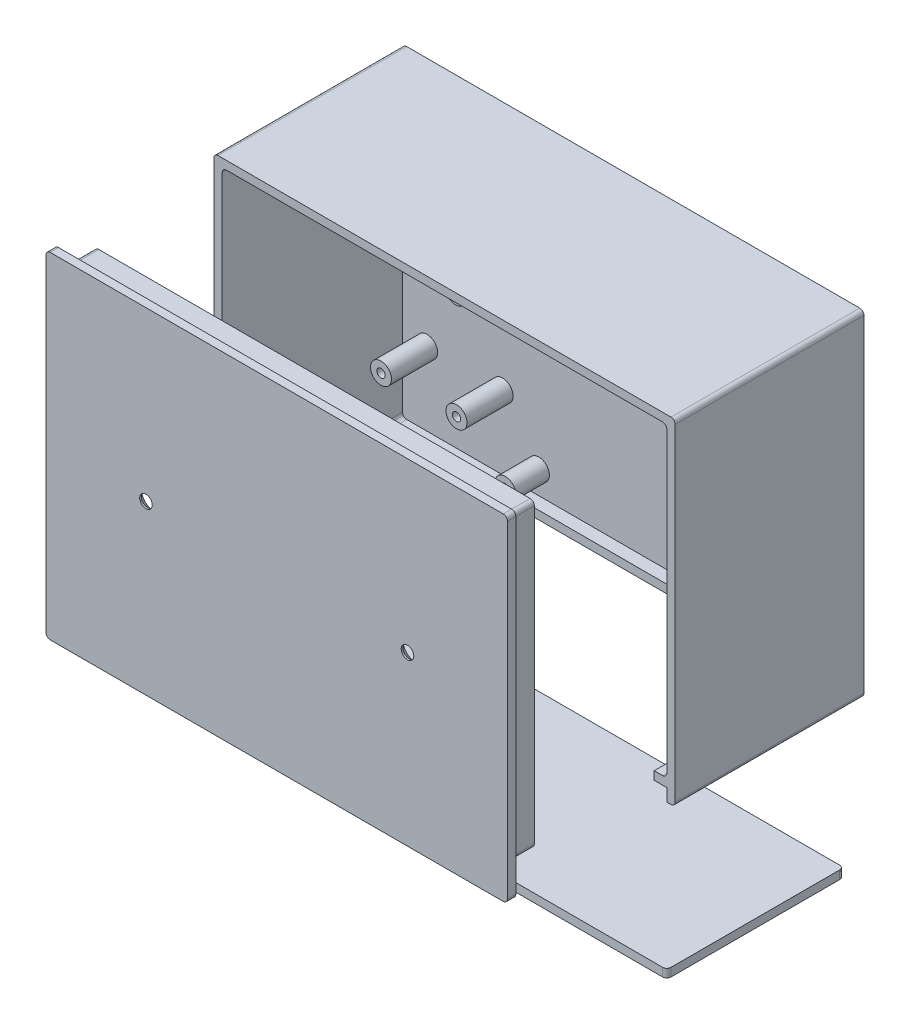
SolidWorks part; units mm, degrees
ref_plane "Спереди" through (0, 0, 0) normal (0, 0, 1) x (1, 0, 0)
ref_plane "Сверху" through (0, 0, 0) normal (0, 1, 0) x (1, 0, 0)
ref_plane "Справа" through (0, 0, 0) normal (1, 0, 0) x (0, 0, -1)
sketch "Эскиз1" plane through (0, 0, 0) normal (0, 0, 1) x (1, 0, 0)
  line L0 (-55, -41.511) -> (-53, -41.511)
  line L2 (-55, 38.489) -> (-55, -41.511)
  line L5 (-55, 38.489) -> (55, 38.489)
  line L6 (53, -36.511) -> (53, 36.489)
  line L7 (-53, -41.511) -> (-53, -38.511)
  line L8 (-53, -38.511) -> (-50, -38.511)
  line L9 (-50, -38.511) -> (-50, -36.511)
  line L10 (-50, -36.511) -> (-53, -36.511)
  line L11 (-53, -36.511) -> (-53, 36.489)
  line L12 (-53, 36.489) -> (53, 36.489)
  line L13 (0, 55.7111) -> (0, -96.3987) construction
  line L14 (50, -36.511) -> (53, -36.511)
  line L15 (50, -38.511) -> (50, -36.511)
  line L16 (53, -38.511) -> (50, -38.511)
  line L17 (53, -41.511) -> (53, -38.511)
  line L18 (55, 38.489) -> (55, -41.511)
  line L19 (55, -41.511) -> (53, -41.511)
  point P0 (0, 0)
  point P15 (0, 36.489)
  point P21 (0, 38.489)
  dimension "D1" = 2
  dimension "D2" = 2
  dimension "D3" = 2
  dimension "D4" = 55
  dimension "D5" = 80
  dimension "D6" = 2
  dimension "D7" = 3
  dimension "D8" = 3
extrude "Бобышка-Вытянуть3" add sketch "Эскиз1" along normal blind 43
sketch "Эскиз2" plane through (0, 0, 0) normal (0, 0, -1) x (-1, 0, 0)
  line L36 (55, 38.489) -> (55, -41.511) construction
  line L37 (-55, 38.489) -> (55, 38.489) construction
  line L38 (-55, -41.511) -> (-55, 38.489) construction
  line L39 (55, 38.489) -> (55, -41.511)
  line L40 (-55, 38.489) -> (55, 38.489)
  line L41 (-55, -41.511) -> (-55, 38.489)
  line L42 (-55, -41.511) -> (55, -41.511)
extrude "Бобышка-Вытянуть4" add sketch "Эскиз2" along normal blind 2
ref_plane "Плоскость1" through (0, 0, 8) normal (0, 0, 1) x (1, 0, 0)
sketch "Эскиз3" plane through (0, 0, 8) normal (0, 0, 1) x (1, 0, 0)
  line L0 (-53, -38.511) -> (-50, -38.511) construction
  line L1 (48, -32.511) -> (-23, -32.511) construction
  line L2 (48, -32.511) -> (48, 17.489) construction
  line L3 (48, 17.489) -> (-23, 17.489) construction
  line L4 (-23, -32.511) -> (-23, 17.489) construction
  line L5 (-33.1063, -7.511) -> (53.7568, -7.511) construction
  line L6 (12.5, 27.0434) -> (12.5, -35.2357) construction
  line L8 (50, -38.511) -> (53, -38.511) construction
  line L9 (53, 36.489) -> (53, -36.511) construction
  line L10 (-38.1409, 10.489) -> (-38.1409, -27.511) construction
  line L11 (-49.1409, 10.489) -> (-27.1409, 10.489) construction
  line L12 (-49.1409, 10.489) -> (-49.1409, -27.511) construction
  line L13 (-49.1409, -27.511) -> (-27.1409, -27.511) construction
  line L14 (-27.1409, 10.489) -> (-27.1409, -27.511) construction
  circle A0 centre (-20.5, 15.989) radius 1
  circle A1 centre (-20.5, 15.989) radius 2.5
  circle A2 centre (45.5, 15.989) radius 2.5
  circle A3 centre (45.5, 15.989) radius 1
  circle A4 centre (-20.5, 15.989) radius 1
  circle A5 centre (-20.5, 15.989) radius 2.5
  circle A6 centre (45.5, 15.989) radius 2.5
  circle A7 centre (45.5, 15.989) radius 1
  circle A8 centre (45.5, -31.011) radius 1
  circle A9 centre (45.5, -31.011) radius 2.5
  circle A10 centre (-20.5, -31.011) radius 2.5
  circle A11 centre (-20.5, -31.011) radius 1
  circle A12 centre (45.5, -31.011) radius 1
  circle A13 centre (45.5, -31.011) radius 2.5
  circle A14 centre (-20.5, -31.011) radius 2.5
  circle A15 centre (-20.5, -31.011) radius 1
  circle A16 centre (-47.1409, -19.011) radius 1
  circle A17 centre (-47.1409, -19.011) radius 2.5
  circle A18 centre (-29.1409, -19.011) radius 2.5
  circle A19 centre (-29.1409, -19.011) radius 1
  circle A20 centre (-29.3409, 6.489) radius 2.5
  circle A21 centre (-29.3409, 6.489) radius 1
  point P0 (12.5, -7.511)
  point P35 (12.5, 17.489)
  point P36 (-23, -7.511)
  point P40 (-38.1409, -8.8408)
  dimension "D5" = 2
  dimension "D6" = 5
  dimension "D11" = 2
  dimension "D12" = 5
  dimension "D1" = 50
  dimension "D2" = 71
  dimension "D3" = 6
  dimension "D4" = 5
  dimension "D7" = 47
  dimension "D8" = 66
  dimension "D9" = 38
  dimension "D10" = 22
  dimension "D13" = 8.5
  dimension "D14" = 18
  dimension "D15" = 4
  dimension "D16" = 2.2
  dimension "D17" = 11
extrude "Бобышка-Вытянуть2" add sketch "Эскиз3" against normal up to surface (8 mm away) contours A1 | A10 | A11 | A2 | A3 | A9 | A8 | A0 up to face at (0, -25.8443, 0)
sketch "Эскиз4" plane through (0, 0, 0) normal (0, 0, 1) x (1, 0, 0)
  line L0 (-50, -36.511) -> (-50, -38.511)
  line L1 (-50, -38.511) -> (50, -38.511)
  line L2 (50, -38.511) -> (50, -36.511)
  line L3 (50, -36.511) -> (-50, -36.511)
extrude "Бобышка-Вытянуть5" add sketch "Эскиз4" along normal blind 3
ref_plane "Плоскость2" through (0, 0, 83) normal (0, 0, 1) x (1, 0, 0)
sketch "Эскиз5" plane through (0, 0, 83) normal (0, 0, 1) x (1, 0, 0)
  line L0 (55, -41.511) -> (55, 38.489) construction
  line L1 (55, 38.489) -> (-55, 38.489) construction
  line L2 (-55, 38.489) -> (-55, -41.511) construction
  line L3 (55, -41.511) -> (55, 38.489)
  line L4 (55, 38.489) -> (-55, 38.489)
  line L5 (-55, 38.489) -> (-55, -41.511)
  line L6 (-55, -41.511) -> (55, -41.511)
  line L7 (-55, -1.511) -> (66.1555, -1.511) construction
  line L8 (0, 36.489) -> (0, -47.4003) construction
  line L9 (-53, 36.489) -> (53, 36.489) construction
  circle A0 centre (-31.1737, -1.511) radius 1.5
  circle A1 centre (31.1737, -1.511) radius 1.5
  dimension "D1" = 3
extrude "Бобышка-Вытянуть6" add sketch "Эскиз5" against normal blind 2 separate body
sketch "Эскиз6" plane through (0, 0, 83) normal (0, 0, 1) x (1, 0, 0)
  line L0 (-50.4, 33.889) -> (50.4, 33.889)
  line L1 (50.4, 33.889) -> (50.4, -33.911)
  line L2 (50.4, -33.911) -> (50, -33.911)
  line L3 (0, 55.7111) -> (0, -96.3987) construction
  line L4 (50, -33.911) -> (50, -35.911)
  line L5 (49.6, -36.511) -> (49.6, -38.511)
  line L6 (-49.6, -38.511) -> (-49.6, -36.511)
  line L24 (-50, -35.911) -> (-50, -33.911)
  line L25 (-50, -33.911) -> (-50.4, -33.911)
  line L26 (-50.4, -33.911) -> (-50.4, 33.889)
  line L31 (52.4, -35.911) -> (50, -35.911)
  line L32 (52.4, 35.889) -> (52.4, -35.911)
  line L33 (-52.4, 35.889) -> (52.4, 35.889)
  line L34 (49.6, -36.511) -> (-49.6, -36.511)
  line L35 (-49.6, -38.511) -> (49.6, -38.511)
  line L36 (-52.4, -35.911) -> (-52.4, 35.889)
  line L37 (-50, -35.911) -> (-52.4, -35.911)
  line L38 (52.4, -35.911) -> (50, -35.911)
  line L39 (52.4, 35.889) -> (52.4, -35.911)
  line L40 (-52.4, 35.889) -> (52.4, 35.889)
  line L41 (-52.4, -35.911) -> (-52.4, 35.889)
  line L42 (-50, -35.911) -> (-52.4, -35.911)
  point P0 (0, -38.511)
  dimension "D1" = 99.2
  dimension "D3" = 2
  dimension "D4" = 2
  dimension "D5" = 2
  dimension "D6" = 2
  dimension "D7" = 2
  dimension "D2" = 0.6
extrude "Бобышка-Вытянуть7" add sketch "Эскиз6" against normal blind 9 contours L42 L24 L25 L26 L0 L1 L2 L4 L38 L39 L40 L41 region at (-51.6704, -0.011, 83)
extrude "Бобышка-Вытянуть8" add sketch "Эскиз6<3>" against normal blind 5 contours L6 L35 L5 L34 region at (0, -37.511, 83)
sketch "Эскиз6<3>" plane through (0, 0, 83) normal (0, 0, 1) x (1, 0, 0) same geometry as "Эскиз6"
ref_plane "Плоскость3" through (0, -78.511, 0) normal (0, -1, 0) x (-1, 0, 0)
sketch "Эскиз10" plane through (0, -78.511, 0) normal (0, -1, 0) x (-1, 0, 0)
  line L4 (50, -43) -> (50, -3) construction
  line L5 (-50, -3) -> (50, -3) construction
  line L6 (-50, -3) -> (-50, -39.4) construction
  line L7 (-50, -39.4) -> (50, -39.4) construction
  line L8 (-52.6, -42.6) -> (52.6, -42.6)
  line L9 (52.6, -42.6) -> (52.6, -0.4)
  line L10 (52.6, -0.4) -> (-52.6, -0.4)
  line L11 (-52.6, -0.4) -> (-52.6, -42.6)
  line L12 (-52.6, -42.6) -> (52.6, -42.6)
  line L13 (52.6, -42.6) -> (52.6, -0.4)
  line L14 (52.6, -0.4) -> (-52.6, -0.4)
  line L15 (-52.6, -0.4) -> (-52.6, -42.6)
  line L16 (50, -3) -> (50, -39.4) construction
  line L17 (-50, -3) -> (50, -39.4) construction
  line L18 (-50, -39.4) -> (50, -3) construction
  point P4 (0, -21.2)
  dimension "D2" = 3.2
  dimension "D1" = 0.4
extrude "Бобышка-Вытянуть9" add sketch "Эскиз10" against normal blind 2 separate body
chamfer "Фаска1" distance 1.6 angle 45 2 edges at (29.6737, -1.511, 81) (-29.6737, -1.511, 81)
fillet "Скругление1" radius 1 8 edges at (-53, -36.511, 21.5) (-53, 36.489, 21.5) (53, 36.489, 21.5) (53, -36.511, 21.5) (-55, -41.511, 20.5) (55, -41.511, 20.5) (55, 38.489, 20.5) (-55, 38.489, 20.5)
fillet "Скругление2" radius 1 10 edges at (-55, -41.511, 82) (55, -41.511, 82) (55, 38.489, 82) (-55, 38.489, 82) (52.4, 35.889, 77.5) (50, -35.911, 77.5) (52.4, -35.911, 77.5) (-50, -35.911, 77.5) (-52.4, -35.911, 77.5) (-52.4, 35.889, 77.5)
fillet "Скругление3" radius 1 4 edges at (-52.6, -77.511, 0.4) (-52.6, -77.511, 42.6) (52.6, -77.511, 42.6) (52.6, -77.511, 0.4)
extrude "Бобышка-Вытянуть10" add sketch "Эскиз3<3>" against normal up to surface (10 mm away) from offset 3 contours A17 | A16 | A19 | A18 | A20 | A21 up to face at (0, -1.511, -2)
sketch "Эскиз3<3>" plane through (0, 0, 8) normal (0, 0, 1) x (1, 0, 0) same geometry as "Эскиз3"
equation "\"D5@Эскиз6\"=\"D4@Эскиз6\""
equation "\"D6@Эскиз6\"=\"D4@Эскиз6\""
equation "\"D7@Эскиз6\"=\"D4@Эскиз6\""
equation "\"D3@Эскиз6\"=\"D4@Эскиз6\""
